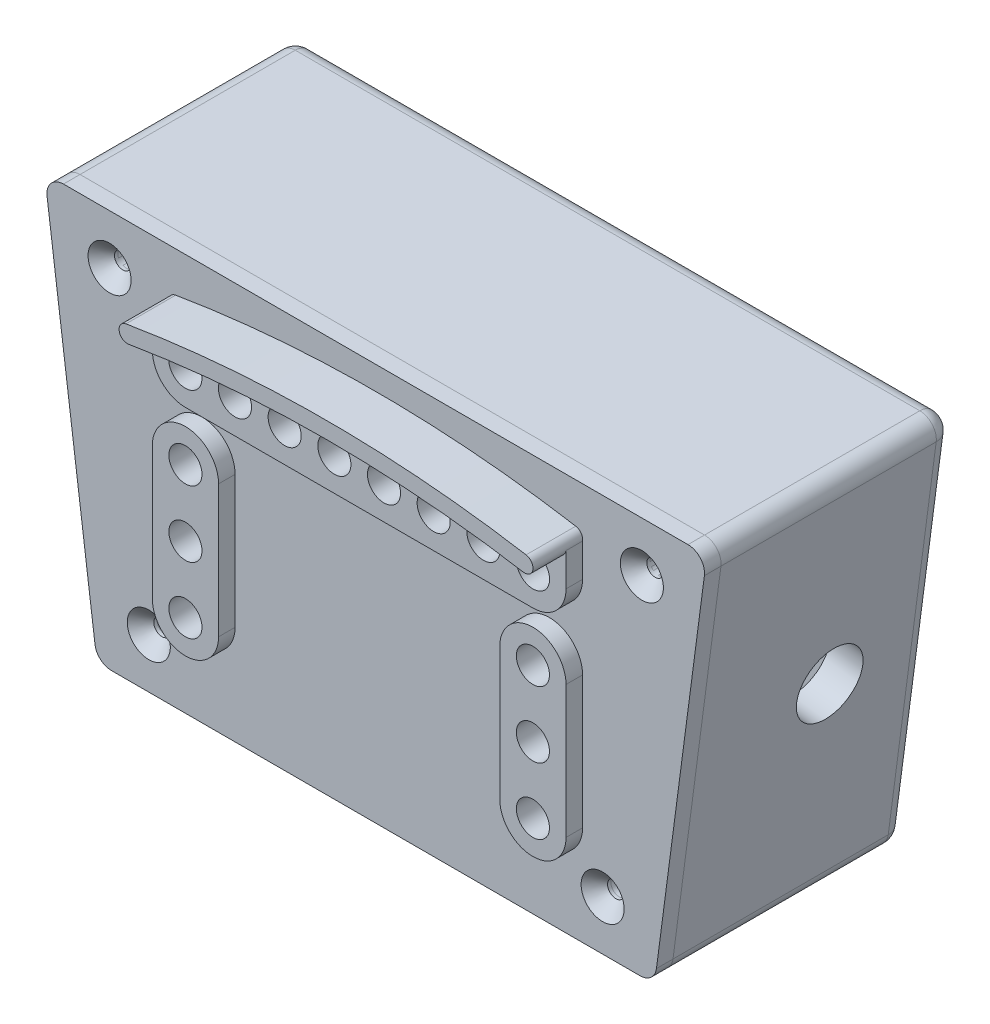
SolidWorks part; units mm, degrees
material "Nylon 101"
ref_plane "Front Plane" through (0, 0, 0) normal (0, 0, 1) x (1, 0, 0)
ref_plane "Top Plane" through (0, 0, 0) normal (0, 1, 0) x (1, 0, 0)
ref_plane "Right Plane" through (0, 0, 0) normal (1, 0, 0) x (0, 0, -1)
sketch "Sketch1" plane through (0, 0, 0) normal (0, 0, 1) x (1, 0, 0)
  line L1 (-53.4681, -38.1) -> (53.4681, -38.1)
  line L2 (-53.4681, -38.1) -> (-63.5, 38.1)
  line L3 (-63.5, 38.1) -> (63.5, 38.1)
  line L4 (53.4681, -38.1) -> (63.5, 38.1)
  line L5 (0, 38.1) -> (0, -38.1) construction
  line L6 (-58.484, 0) -> (58.484, 0) construction
  line L7 (-47.8993, -31.75) -> (47.8993, -31.75)
  line L8 (-47.8993, -31.75) -> (-56.2592, 31.75)
  line L9 (-56.2592, 31.75) -> (56.2592, 31.75)
  line L10 (47.8993, -31.75) -> (56.2592, 31.75)
  line L11 (0, 31.75) -> (0, -31.75) construction
  line L12 (-52.0792, 0) -> (52.0792, 0) construction
  point P0 (0, 0)
  point P4 (0, 0)
  dimension "D1" = 127
  dimension "D2" = 76.2
  dimension "D3" = 6.35
  dimension "D4" = 6.35
  dimension "D5" = 15
extrude "Boss-Extrude1" add sketch "Sketch1" along normal blind 3.175 contours L7 L10 L9 L8 | L1 L4 L3 L2 L10 L7 L8 L9 region at (-57.0156, 0.1933, 0) region at (0, 0.8494, 0)
extrude "Boss-Extrude2" add sketch "Sketch1<3>" against normal blind 3.175 contours L7 L10 L9 L8 region at (0, 0.8494, 0)
sketch "Sketch1<3>" plane through (0, 0, 0) normal (0, 0, 1) x (1, 0, 0) same geometry as "Sketch1"
sketch "Sketch2" plane through (0, 0, 0) normal (0, 0, 1) x (1, 0, 0)
  line L0 (-38.1, 28.8378) -> (0, 0) construction
  line L2 (0, 0) -> (38.1, 28.8378) construction
  line L4 (-33.3375, 22.225) -> (-23.8125, 22.225) construction
  line L5 (-39.6656, 28.575) -> (39.6656, 28.575) construction
  line L6 (-39.6656, 28.575) -> (-39.6656, 15.875)
  line L7 (-39.6656, 15.875) -> (39.6656, 15.875)
  line L8 (39.6656, 28.575) -> (39.6656, 15.875)
  line L9 (0, 22.225) -> (0, 0) construction
  line L10 (-33.3375, 22.225) -> (33.3375, 22.225) construction
  line L11 (-63.5, 38.1) -> (63.5, 38.1) construction
  arc A5 (-38.1, 28.8378) -> (38.1, 28.8378) centre (0, -198.1747) cw construction
  arc A6 (-37.8372, 27.2722) -> (37.8372, 27.2722) centre (0, -198.1747) cw
  arc A7 (-38.3628, 30.4034) -> (38.3628, 30.4034) centre (0, -198.1747) cw
  arc A8 (-37.8372, 27.2722) -> (-38.3628, 30.4034) centre (-38.1, 28.8378) cw
  arc A9 (37.8372, 27.2722) -> (38.3628, 30.4034) centre (38.1, 28.8378) ccw
  circle A10 centre (-33.3375, 22.225) radius 3.175
  circle A11 centre (-23.8125, 22.225) radius 3.175
  circle A12 centre (-14.2875, 22.225) radius 3.175
  circle A13 centre (-4.7625, 22.225) radius 3.175
  circle A14 centre (4.7625, 22.225) radius 3.175
  circle A15 centre (14.2875, 22.225) radius 3.175
  circle A16 centre (23.8125, 22.225) radius 3.175
  circle A17 centre (33.3375, 22.225) radius 3.175
  point P7 (0, 22.225)
  point P8 (39.6656, 22.225)
  point P9 (0, 32.0128)
  dimension "D1" = 15.875
  dimension "D3" = 3.175
  dimension "D4" = 1.5875
  dimension "D7" = 6.35
  dimension "D8" = 8
  dimension "D5" = 1.5875
  dimension "D2" = 76.2
  dimension "D6" = 12.7
  dimension "D9" = 9.525
extrude "Boss-Extrude3" add sketch "Sketch2" along normal blind 6.35 contours A9 A6 A8 L6 L7 L8 A17 A16 A15 A14 A13 A12 A11 A10 | A10 | A11 | A12 | A13 | A14 | A15 | A16 | A17 | A6 A9 A7 A8 region at (0, 22.7442, 0) region at (0, 30.8867, 0) region at (-33.3375, 22.225, 0) region at (-23.8125, 22.225, 0) region at (-14.2875, 22.225, 0) region at (-4.7625, 22.225, 0) region at (4.7625, 22.225, 0) region at (14.2875, 22.225, 0) region at (23.8125, 22.225, 0) region at (33.3375, 22.225, 0)
extrude "Boss-Extrude4" add sketch "Sketch2<3>" along normal blind 12.7 contours A6 A9 A7 A8 region at (0, 30.8867, 0)
sketch "Sketch2<3>" plane through (0, 0, 0) normal (0, 0, 1) x (1, 0, 0) same geometry as "Sketch2"
extrude "Cut-Extrude1" cut sketch "Sketch2<4>" against normal through all both and the other way through all contours A10 | A11 | A12 | A13 | A14 | A15 | A16 | A17 region at (-33.3375, 22.225, 0) region at (-23.8125, 22.225, 0) region at (-14.2875, 22.225, 0) region at (-4.7625, 22.225, 0) region at (4.7625, 22.225, 0) region at (14.2875, 22.225, 0) region at (23.8125, 22.225, 0) region at (33.3375, 22.225, 0)
sketch "Sketch2<4>" plane through (0, 0, 0) normal (0, 0, 1) x (1, 0, 0) same geometry as "Sketch2"
fillet "Fillet1" radius 6.35 2 edges at (39.6656, 15.875, 4.7625) (-39.6656, 15.875, 4.7625)
sketch "Sketch4" plane through (0, 0, 0) normal (0, 0, 1) x (1, 0, 0)
  line L0 (0, 0) -> (0, -19.05) construction
  line L1 (-33.3156, 6.35) -> (33.3156, 6.35) construction
  line L2 (-33.3156, 6.35) -> (-33.3156, -19.05) construction
  line L3 (-33.3156, -19.05) -> (33.3156, -19.05) construction
  line L4 (33.3156, 6.35) -> (33.3156, -19.05) construction
  line L5 (-63.5, 38.1) -> (63.5, 38.1) construction
  line L6 (-33.3156, 6.35) -> (-33.3156, -19.05) construction
  line L7 (-26.9656, 6.35) -> (-26.9656, -19.05)
  line L8 (-39.6656, 6.35) -> (-39.6656, -19.05)
  line L9 (33.3156, 6.35) -> (33.3156, -19.05) construction
  line L10 (39.6656, 6.35) -> (39.6656, -19.05)
  line L11 (26.9656, 6.35) -> (26.9656, -19.05)
  line L12 (-39.6656, 22.225) -> (-39.6656, 28.575) construction
  circle A0 centre (-33.3156, 6.35) radius 3.175
  circle A1 centre (-33.3156, -6.35) radius 3.175
  circle A2 centre (-33.3156, -19.05) radius 3.175
  circle A3 centre (33.3156, 6.35) radius 3.175
  circle A4 centre (33.3156, -6.35) radius 3.175
  circle A5 centre (33.3156, -19.05) radius 3.175
  arc A12 (-26.9656, 6.35) -> (-39.6656, 6.35) centre (-33.3156, 6.35) ccw
  arc A13 (-39.6656, -19.05) -> (-26.9656, -19.05) centre (-33.3156, -19.05) ccw
  arc A14 (39.6656, 6.35) -> (26.9656, 6.35) centre (33.3156, 6.35) ccw
  arc A15 (26.9656, -19.05) -> (39.6656, -19.05) centre (33.3156, -19.05) ccw
  point P4 (-33.3156, -6.35)
  point P22 (33.3156, -6.35)
  dimension "D1" = 6.35
  dimension "D5" = 3.175
  dimension "D2" = 12.7
  dimension "D3" = 31.75
extrude "Boss-Extrude5" add sketch "Sketch4" along normal blind 6.35
extrude "Cut-Extrude2" cut sketch "Sketch4<2>" along normal through all both and the other way through all contours A0 | A1 | A2 | A5 | A4 | A3 region at (-33.3156, 6.35, 0) region at (-33.3156, -6.35, 0) region at (-33.3156, -19.05, 0) region at (33.3156, 6.35, 0) region at (33.3156, -6.35, 0) region at (33.3156, -19.05, 0)
sketch "Sketch4<2>" plane through (0, 0, 0) normal (0, 0, 1) x (1, 0, 0) same geometry as "Sketch4"
extrude "Boss-Extrude6" add sketch "Sketch1<4>" against normal blind 38.1 separate body contours L1 L4 L3 L2 L10 L7 L8 L9 region at (-57.0156, 0.1933, 0)
sketch "Sketch1<4>" plane through (0, 0, 0) normal (0, 0, 1) x (1, 0, 0) same geometry as "Sketch1"
extrude "Boss-Extrude7" add sketch "Sketch1<5>" against normal blind 6.35 from surface contours L7 L10 L9 L8 | L1 L4 L3 L2 L10 L7 L8 L9 region at (-57.0156, 0.1933, 0) region at (0, 0.8494, 0) starting at face at (0, 0, -38.1)
sketch "Sketch1<5>" plane through (0, 0, 0) normal (0, 0, 1) x (1, 0, 0) same geometry as "Sketch1"
sketch "Sketch5" plane through (0, 0, 0) normal (0, 0, 1) x (1, 0, 0)
  line L1 (-43.5137, -28.575) -> (43.5137, -28.575) construction
  line L2 (-43.5137, -28.575) -> (-51.0376, 28.575) construction
  line L3 (-51.0376, 28.575) -> (51.0376, 28.575) construction
  line L4 (-47.8993, -31.75) -> (47.8993, -31.75)
  line L5 (47.8993, -31.75) -> (56.2592, 31.75)
  line L6 (56.2592, 31.75) -> (-56.2592, 31.75)
  line L7 (-56.2592, 31.75) -> (-47.8993, -31.75)
  line L8 (-47.8993, -31.75) -> (47.8993, -31.75)
  line L9 (47.8993, -31.75) -> (56.2592, 31.75)
  line L10 (56.2592, 31.75) -> (-56.2592, 31.75)
  line L11 (-56.2592, 31.75) -> (-47.8993, -31.75)
  line L12 (43.5137, -28.575) -> (51.0376, 28.575) construction
  line L13 (0, 28.575) -> (0, -28.575) construction
  line L14 (-47.2757, 0) -> (47.2757, 0) construction
  circle A0 centre (-51.0376, 28.575) radius 1.5875
  circle A1 centre (51.0376, 28.575) radius 1.5875
  circle A2 centre (43.5137, -28.575) radius 1.5875
  circle A3 centre (-43.5137, -28.575) radius 1.5875
  circle A4 centre (-51.0376, 28.575) radius 6.35
  circle A5 centre (-43.5137, -28.575) radius 6.35
  circle A6 centre (43.5137, -28.575) radius 6.35
  circle A7 centre (51.0376, 28.575) radius 6.35
  point P2 (0, 0)
  dimension "D2" = 4.7625
  dimension "D3" = 3.175
  dimension "D4" = 3.175
  dimension "D5" = 3.175
  dimension "D1" = 0
extrude "Boss-Extrude11" add sketch "Sketch5" against normal through all contours L11 A4 L10 A0 | L8 A5 L11 A3 | L9 A6 L8 A2 | L10 A7 L9 A1 region at (-48.1925, -28.3716, 0) region at (40.2325, -23.3147, 0) region at (-55.5866, 27.7891, 0) region at (47.0976, 23.7877, 0)
extrude "Cut-Extrude9" cut sketch "Sketch5<4>" along normal through all both and the other way through all contours A0 | A3 | A2 | A1 region at (-51.0376, 28.575, 0) region at (51.0376, 28.575, 0) region at (43.5137, -28.575, 0) region at (-43.5137, -28.575, 0)
sketch "Sketch5<4>" plane through (0, 0, 0) normal (0, 0, 1) x (1, 0, 0) same geometry as "Sketch5"
sketch "Sketch6" plane through (-2.7734, -465.2965, 0) normal (-0.9914, 0.1305, 0) x (0, 0, -1)
  line L0 (25.4, -469.3116) -> (0, -469.3116) construction
  line L1 (0, -430.8828) -> (0, -507.7403) construction
  line L4 (44.45, -430.8828) -> (44.45, -507.7403) construction
  circle A0 centre (25.4, -469.3116) radius 6.35
  dimension "D1" = 12.7
  dimension "D2" = 19.05
extrude "Cut-Extrude10" cut sketch "Sketch6" along normal up to next (6.35 mm away) and the other way through all contours A0
chamfer "Chamfer1" distance 2.54 angle 45 4 edges at (52.6251, 28.575, 3.175) (45.1012, -28.575, 3.175) (-41.9262, -28.575, 3.175) (-49.4501, 28.575, 3.175)
fillet "Fillet2" radius 3.175 8 edges at (0, -38.1, -44.45) (58.484, 0, -44.45) (0, 38.1, -44.45) (-58.484, 0, -44.45) (53.4681, -38.1, -22.225) (63.5, 38.1, -22.225) (-53.4681, -38.1, -22.225) (-63.5, 38.1, -22.225)
fillet "Fillet3" radius 3.175 4 edges at (-53.4681, -38.1, 1.5875) (-63.5, 38.1, 1.5875) (63.5, 38.1, 1.5875) (53.4681, -38.1, 1.5875)
